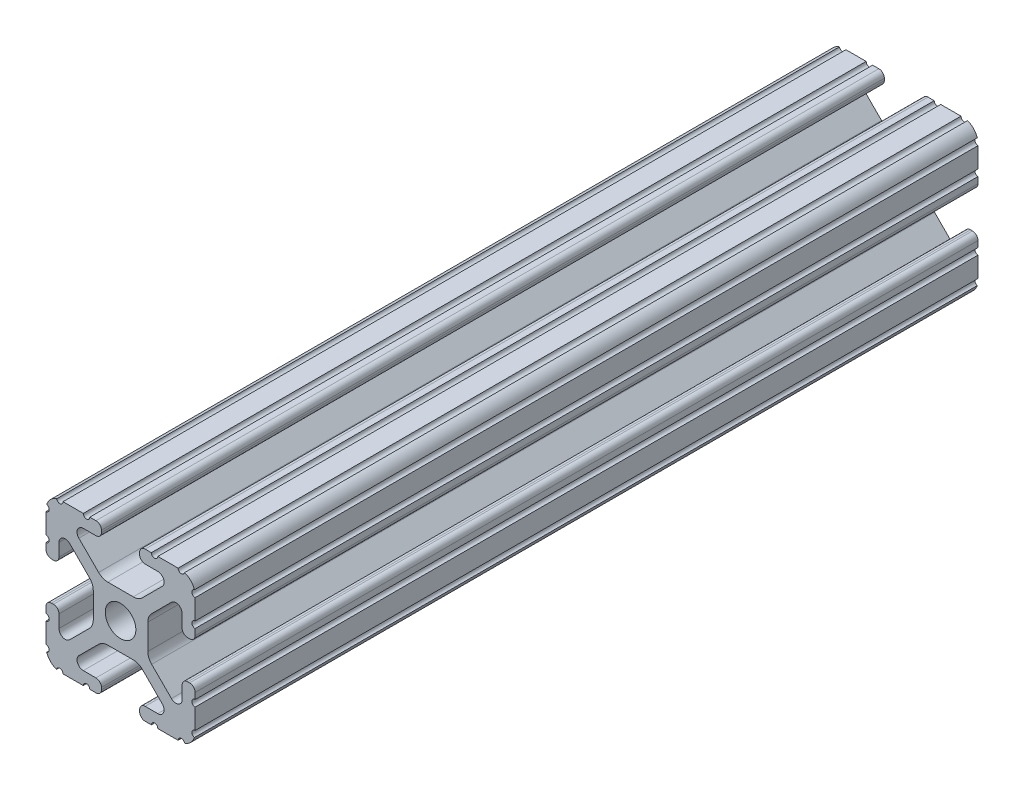
SolidWorks part; units mm, degrees
ref_plane "Front Plane" through (0, 0, 0) normal (0, 0, 1) x (1, 0, 0)
ref_plane "Top Plane" through (0, 0, 0) normal (0, 1, 0) x (1, 0, 0)
ref_plane "Right Plane" through (0, 0, 0) normal (1, 0, 0) x (0, 0, -1)
sketch "Sketch2" plane through (0, 0, 0) normal (0, 0, 1) x (1, 0, 0)
  line L0 (0, 12.7) -> (0, -12.7) construction
  line L1 (-12.7, 0) -> (12.7, 0) construction
  line L2 (3.2512, -12.7) -> (12.7, -12.7)
  line L3 (12.7, -12.7) -> (12.7, -3.2512)
  line L4 (3.2512, -12.7) -> (3.2512, -10.4902)
  line L5 (3.2512, -10.4902) -> (8.9276, -10.4902)
  line L6 (8.9276, -10.4902) -> (3.0856, -4.6482)
  line L7 (0, 0) -> (12.7, -12.7) construction
  line L8 (12.7, -3.2512) -> (10.4902, -3.2512)
  line L9 (10.4902, -3.2512) -> (10.4902, -8.9276)
  line L10 (10.4902, -8.9276) -> (4.6482, -3.0856)
  circle A0 centre (0, 0) radius 2.6035
  arc A1 (6.3485, -10.4902) -> (7.1039, -8.6665) centre (6.3485, -9.4219) ccw construction
  point P8 (0, -4.6482)
  dimension "Center Hole Diameter" = 5.207
  dimension "Rail Height" = 25.4
  dimension "Rail Width" = 25.4
  dimension "T-Slot Width" = 6.5024
  dimension "Slot Inner Width" = 14.8336
  dimension "Thickness" = 2.2098
  dimension "Slot Depth" = 5.842
  dimension "D1" = 2.2098
sketch "Sketch3" plane through (0, 0, 0) normal (1, 0, 0) x (0, 0, -1)
  line L0 (-66.675, -12.7) -> (66.675, -12.7) construction
  line L1 (-41.275, 0) -> (41.275, 0) construction
  line L3 (66.675, 0) -> (-66.675, 0) construction
sketch "Sketch4" plane through (0, 0, 0) normal (0, 0, 1) x (1, 0, 0)
  line L0 (4.1904, -12.7) -> (10.1173, -12.7)
  line L1 (3.2512, -12.7) -> (12.7, -12.7) construction
  line L2 (3.2512, -12.7) -> (3.2512, -10.4902) construction
  line L3 (3.2512, -10.4902) -> (8.9276, -10.4902) construction
  line L4 (3.2512, -11.4294) -> (3.2512, -11.7608)
  line L5 (4.1904, -10.4902) -> (6.3485, -10.4902)
  line L6 (0, -4.6482) -> (2.164, -4.6482)
  line L7 (8.9276, -10.4902) -> (3.0856, -4.6482) construction
  line L8 (3.7373, -5.2999) -> (7.1039, -8.6665)
  line L9 (12.7, -12.7) -> (12.7, -3.2512) construction
  line L10 (10.4902, -8.9276) -> (4.6482, -3.0856) construction
  line L11 (10.4902, -3.2512) -> (10.4902, -8.9276) construction
  line L12 (10.4902, -6.3485) -> (10.4902, -4.1904)
  line L13 (12.7, -3.2512) -> (10.4902, -3.2512) construction
  line L14 (11.4294, -3.2512) -> (11.7608, -3.2512)
  line L15 (12.7, -4.1904) -> (12.7, -10.1173)
  line L16 (8.6665, -7.1039) -> (5.2999, -3.7373)
  line L17 (4.6482, 0) -> (4.6482, -2.164)
  line L18 (-12.7, 0) -> (12.7, 0) construction
  line L19 (0, -4.6482) -> (0, -2.6035)
  line L20 (0, 12.7) -> (0, -12.7) construction
  line L21 (4.6482, 0) -> (2.6035, 0)
  arc A0 (3.2512, -11.7608) -> (4.1904, -12.7) centre (4.1904, -11.7608) ccw
  arc A2 (3.2512, -11.4294) -> (4.1904, -10.4902) centre (4.1904, -11.4294) cw
  arc A3 (6.3485, -10.4902) -> (7.1039, -8.6665) centre (6.3485, -9.4219) ccw
  arc A4 (2.164, -4.6482) -> (3.7373, -5.2999) centre (2.164, -6.8732) cw
  arc A5 (10.1173, -12.7) -> (12.7, -10.1173) centre (10.1173, -10.1173) ccw
  arc A6 (8.6665, -7.1039) -> (10.4902, -6.3485) centre (9.4219, -6.3485) ccw
  arc A7 (10.4902, -4.1904) -> (11.4294, -3.2512) centre (11.4294, -4.1904) cw
  arc A8 (11.7608, -3.2512) -> (12.7, -4.1904) centre (11.7608, -4.1904) cw
  arc A9 (5.2999, -3.7373) -> (4.6482, -2.164) centre (6.8732, -2.164) cw
  circle A10 centre (0, 0) radius 2.6035 construction
  arc A11 (0, -2.6035) -> (2.6035, 0) centre (0, 0) ccw
  dimension "D1" = 2.5827
  dimension "D2" = 2.225
  dimension "D3" = 0.9392
extrude "Boss-Extrude1" add sketch "Sketch4" along normal up to vertex (66.675 mm away) from vertex up to point (0, -12.7, 66.675) starting at point (0, -12.7, -66.675)
sketch "Sketch5" plane through (0, 0, 0) normal (0, 0, 1) x (1, 0, 0)
  line L0 (3.2512, -12.7) -> (12.7, -12.7) construction
  line L1 (4.1904, -10.4902) -> (6.3485, -10.4902) construction
  line L3 (0, 0) -> (12.7, -12.7) construction
  line L4 (6.3485, -10.4902) -> (6.3485, -12.7) construction
  line L5 (8.9276, -10.4902) -> (3.0856, -4.6482) construction
  circle A0 centre (10.3562, -12.7) radius 0.5524
  circle A1 centre (5.796, -12.7) radius 0.5524
  circle A2 centre (12.7, -10.3562) radius 0.5524
  circle A3 centre (12.7, -5.796) radius 0.5524
  point P10 (5.2694, -10.4902)
  point P12 (9.4219, -6.3485)
  dimension "D1" = 1.1049
extrude "Cut-Extrude1" cut sketch "Sketch5" against normal through all both and the other way through all
mirror "Mirror1" about plane through (0, 0, 0) normal (1, 0, 0) of bodies 137 134
mirror "Mirror2" about plane through (0, 0, 0) normal (0, 1, 0) of bodies 135
equation "\"D1@Sketch2\"=\"Thickness@Sketch2\""
equation "\"D2@Sketch4\"=\"Slot Inner Width@Sketch2\"*0.15"
equation "\"D1@Sketch4\"=\"D3@Sketch4\"*2.75"
equation "\"D3@Sketch4\"=\"Thickness@Sketch2\"*0.425"
equation "\"D1@Sketch5\"=\"Thickness@Sketch2\"*0.5"
equation "\"D1@Boss-Extrude1\"=\"Length@Sketch3\""
